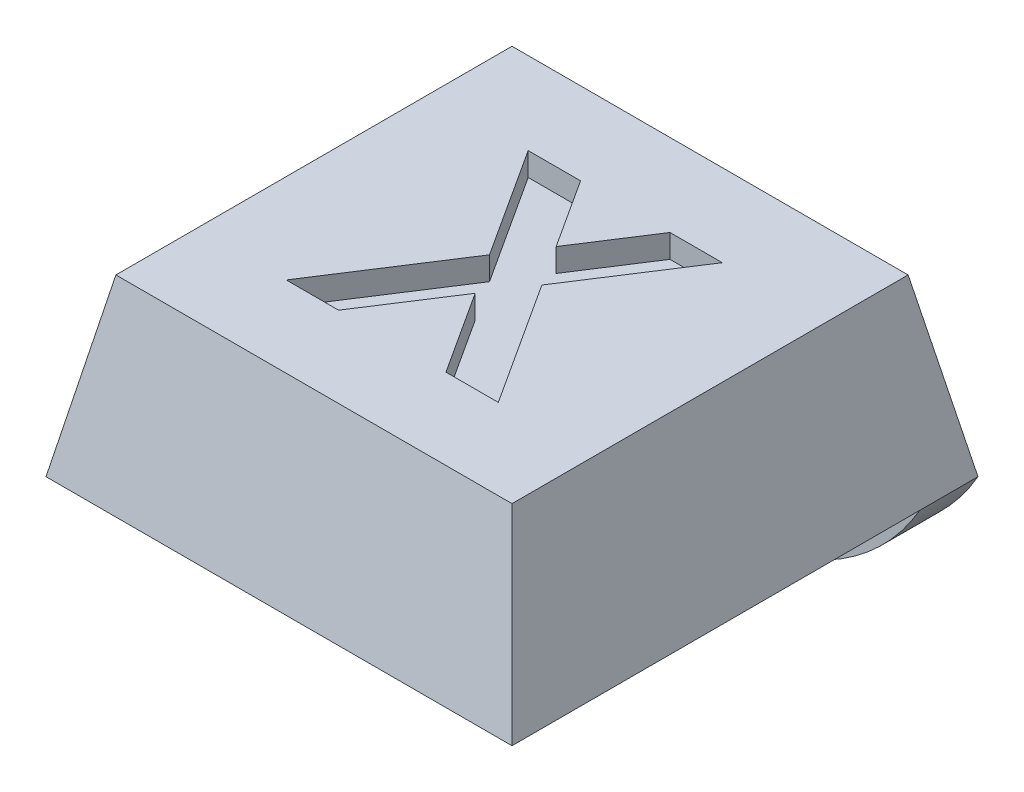
SolidWorks part; units mm, degrees
ref_plane "Front Plane" through (0, 0, 0) normal (0, 0, 1) x (1, 0, 0)
ref_plane "Top Plane" through (0, 0, 0) normal (0, 1, 0) x (1, 0, 0)
ref_plane "Right Plane" through (0, 0, 0) normal (1, 0, 0) x (0, 0, -1)
sketch "Sketch1" plane through (0, 0, 0) normal (0, 1, 0) x (1, 0, 0)
  line L1 (0, 0) -> (8, 0)
  line L2 (0, 0) -> (0, 8)
  line L3 (0, 8) -> (8, 8)
  line L4 (8, 0) -> (8, 8)
  dimension "D1" = 8
  dimension "D2" = 8
extrude "Boss-Extrude1" add sketch "Sketch1" along normal blind 3
sketch "Sketch2" plane through (0, 0, 0) normal (0, 0, 1) x (1, 0, 0)
  line L0 (0, 0) -> (0.6, 3)
  line L1 (0, 3) -> (8, 3) construction
  line L2 (0.6, 3) -> (0, 3)
  line L3 (0, 3) -> (0, 0)
  line L4 (8, 0) -> (7.4, 3)
  line L5 (7.4, 3) -> (8, 3)
  line L6 (8, 3) -> (8, 0)
  dimension "D1" = 0.6
  dimension "D2" = 0.6
extrude "Cut-Extrude1" cut sketch "Sketch2" against normal through all both and the other way through all
sketch "Sketch3" plane through (0, 0, 0) normal (1, 0, 0) x (0, 0, -1)
  line L0 (0, 0) -> (0.6, 3)
  line L1 (8, 3) -> (0, 3) construction
  line L2 (0.6, 3) -> (0, 3)
  line L3 (0, 3) -> (0, 0)
  line L4 (8, 3) -> (7.4, 3)
  line L5 (7.4, 3) -> (8, 0)
  line L6 (8, 3) -> (8, 0)
  dimension "D1" = 0.6
  dimension "D2" = 0.6
extrude "Cut-Extrude2" cut sketch "Sketch3" along normal blind 11
sketch "Sketch4" plane through (0, 0, 0) normal (0, -1, 0) x (1, 0, 0)
  line L0 (8, 0) -> (8, -8) construction
  line L3 (0, 0) -> (8, 0) construction
  circle A0 centre (4, -3.75) radius 1.8
  dimension "D1" = 3.6
  dimension "D2" = 4
  dimension "D3" = 3.75
extrude "Cut-Extrude3" cut sketch "Sketch4" against normal blind 0.8
sketch "Sketch5" plane through (0, 0, 0) normal (0, -1, 0) x (1, 0, 0)
  line L0 (8, 0) -> (8, -8) construction
  line L1 (0, -8) -> (8, -8)
  line L2 (0, -8) -> (0, -7)
  line L3 (0, -7) -> (8, -7)
  line L4 (8, -8) -> (8, -7)
  dimension "D1" = 1
extrude "Boss-Extrude2" add sketch "Sketch5" along normal blind 2
fillet "Fillet1" radius 4 2 edges at (8, -2, -7.5) (0, -2, -7.5)
sketch "Sketch6" plane through (0, 3, 0) normal (0, 1, 0) x (1, 0, 0)
  text T0 "X" font "Arial" height 4
extrude "Cut-Extrude4" cut sketch "Sketch6" against normal blind 0.4
